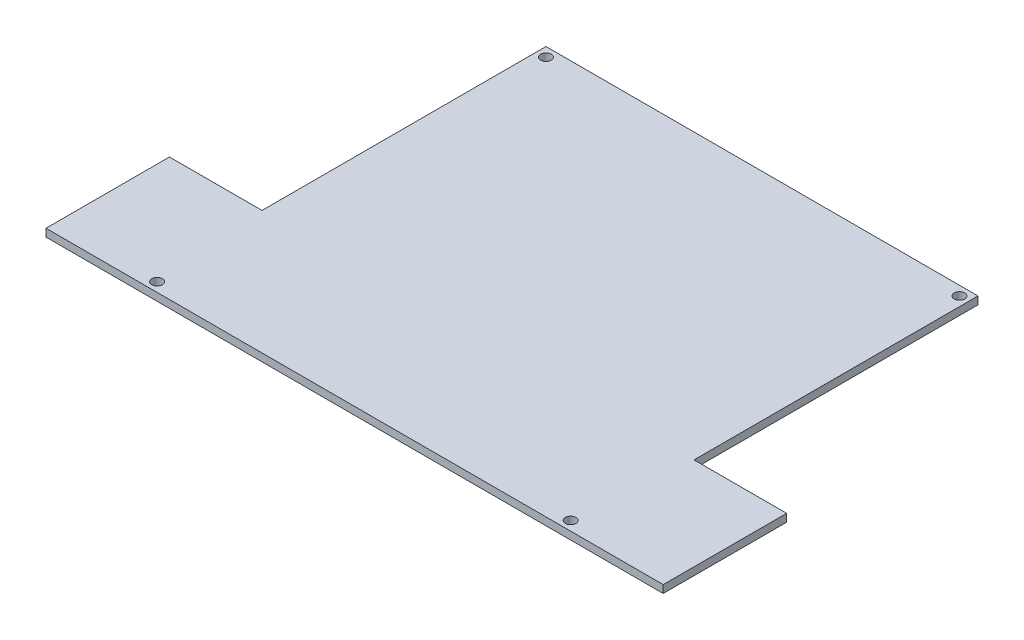
SolidWorks part; units mm, degrees
ref_plane "Front Plane" through (0, 0, 0) normal (0, 0, 1) x (1, 0, 0)
ref_plane "Top Plane" through (0, 0, 0) normal (0, 1, 0) x (1, 0, 0)
ref_plane "Right Plane" through (0, 0, 0) normal (1, 0, 0) x (0, 0, -1)
sketch "Sketch1" plane through (0, 0, 0) normal (0, 1, 0) x (1, 0, 0)
  line L1 (-52.9222, 15.7603) -> (124.8778, 15.7603)
  line L2 (-52.9222, 15.7603) -> (-52.9222, -101.0797)
  line L3 (-52.9222, -151.8797) -> (124.8778, -151.8797)
  line L4 (124.8778, 15.7603) -> (124.8778, -101.0797)
  line L5 (124.8778, -151.8797) -> (162.9778, -151.8797)
  line L7 (124.8778, -101.0797) -> (162.9778, -101.0797)
  line L8 (162.9778, -151.8797) -> (162.9778, -101.0797)
  line L9 (-52.9222, -151.8797) -> (-91.0222, -151.8797)
  line L11 (-52.9222, -101.0797) -> (-91.0222, -101.0797)
  line L12 (-91.0222, -151.8797) -> (-91.0222, -101.0797)
  dimension "D1" = 177.8
  dimension "D2" = 167.64
  dimension "D3" = 38.1
  dimension "D4" = 38.1
  dimension "D5" = 50.8
  dimension "D6" = 50.8
extrude "Boss-Extrude1" add sketch "Sketch1" along normal blind 3.175
sketch "Sketch2" plane through (0, 3.175, 0) normal (0, 1, 0) x (1, 0, 0)
  line L0 (124.8778, 15.7603) -> (-52.9222, 15.7603) construction
  line L1 (-52.9222, 15.7603) -> (-52.9222, -101.0797) construction
  line L2 (124.8778, -101.0797) -> (124.8778, 15.7603) construction
  line L3 (-91.0222, -151.8797) -> (162.9778, -151.8797) construction
  circle A0 centre (-49.1122, 11.9503) radius 2.1717
  circle A1 centre (121.0678, 11.9503) radius 2.1717
  circle A2 centre (-49.1122, -148.0697) radius 2.1717
  circle A3 centre (121.0678, -148.0697) radius 2.1717
  dimension "D1" = 3.81
  dimension "D3" = 3.81
  dimension "D5" = 3.81
  dimension "D7" = 3.81
  dimension "D2" = 3.81
  dimension "D4" = 3.81
  dimension "D6" = 3.81
  dimension "D8" = 3.81
extrude "Cut-Extrude1" cut sketch "Sketch2" against normal blind 3.175
